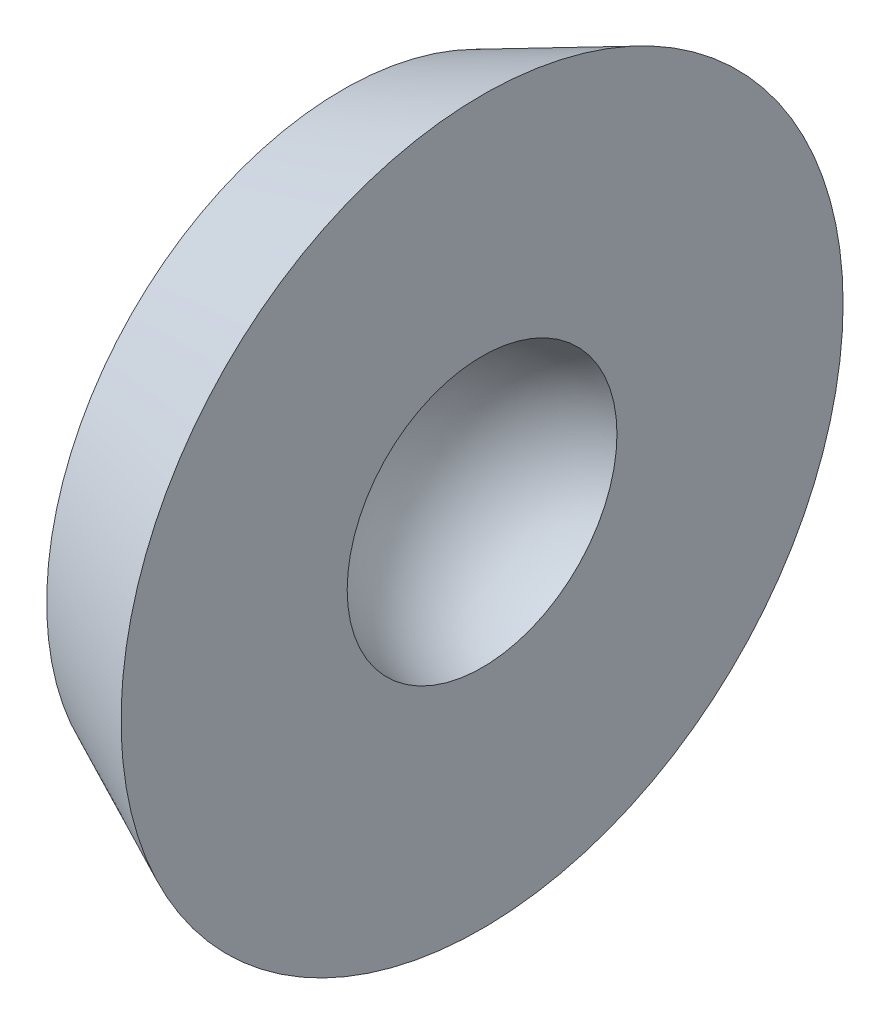
SolidWorks part; units mm, degrees
ref_plane "Front Plane" through (0, 0, 0) normal (0, 0, 1) x (1, 0, 0)
ref_plane "Top Plane" through (0, 0, 0) normal (0, 1, 0) x (1, 0, 0)
ref_plane "Right Plane" through (0, 0, 0) normal (1, 0, 0) x (0, 0, -1)
sketch "Sketch1" plane through (0, 0, 0) normal (1, 0, 0) x (0, 0, -1)
  circle A0 centre (0, 0) radius 4.25
  dimension "D1" = 8.5
extrude "Boss-Extrude1" add sketch "Sketch1" along normal blind 2 draft 25 draft outward yes
sketch "Sketch2" plane through (0, 0, 0) normal (0, 1, 0) x (1, 0, 0)
  line L0 (2, 0) -> (0.5, 0)
  line L1 (2, -5.1826) -> (2, 5.1826) construction
  line L2 (2, 0) -> (2, 1.9365)
  line L3 (2, 0) -> (3.4668, 0) construction
  arc A0 (2, 1.9365) -> (0.5, 0) centre (2.5, 0) ccw
  dimension "D2" = 4
  dimension "D1" = 1.5
revolve "Cut-Revolve1" cut sketch "Sketch2" angle 360 about L3
